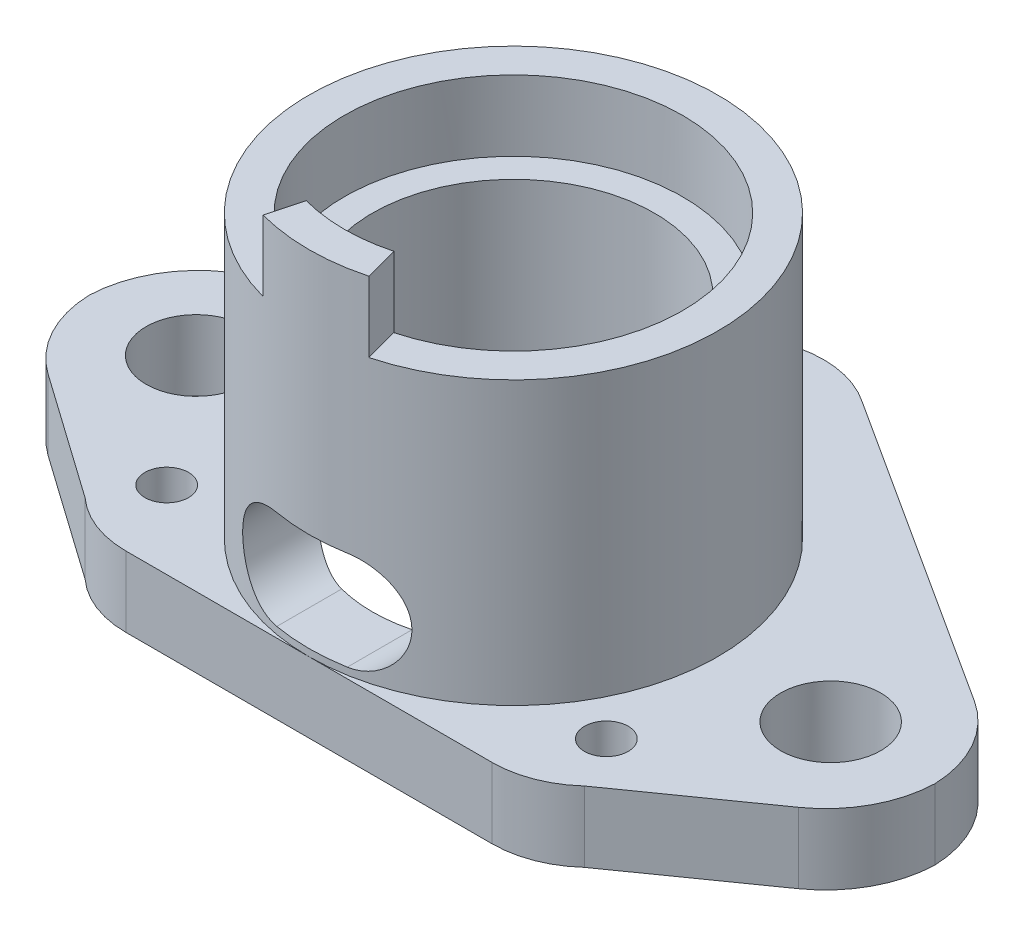
SolidWorks part; units mm, degrees
material "6061 Alloy"
ref_plane "Front Plane" through (0, 0, 0) normal (0, 0, 1) x (1, 0, 0)
ref_plane "Top Plane" through (0, 0, 0) normal (0, 1, 0) x (1, 0, 0)
ref_plane "Right Plane" through (0, 0, 0) normal (1, 0, 0) x (0, 0, -1)
sketch "Sketch1" plane through (0, 0, 0) normal (0, 1, 0) x (1, 0, 0)
  circle A0 centre (0, 0) radius 10
  circle A1 centre (0, 0) radius 14.5
  dimension "D1" = 29
  dimension "D2" = 20
extrude "Boss-Extrude1" add sketch "Sketch1" along normal mid plane 15
sketch "Sketch2" plane through (0, 7.5, 0) normal (0, 1, 0) x (1, 0, 0)
  circle A0 centre (0, 0) radius 14.5
  circle A1 centre (0, 0) radius 12
  dimension "D1" = 29
  dimension "D2" = 24
extrude "Boss-Extrude2" add sketch "Sketch2" along normal blind 5
sketch "Sketch3" plane through (0, -7.5, 0) normal (0, -1, 0) x (-1, 0, 0)
  line L0 (0, 0) -> (0, 38.6793) construction
  line L1 (0, 0) -> (-32.5079, 0) construction
  line L2 (0, 29) -> (-25.1147, -14.5)
  line L3 (-25.1147, -14.5) -> (25.1147, -14.5)
  line L4 (0, 29) -> (25.1147, -14.5)
  line L5 (0, 0) -> (25.1147, -14.5) construction
  circle A0 centre (0, 0) radius 12
  circle A1 centre (15.5885, -9) radius 1.55
  circle A2 centre (-15.5885, -9) radius 1.55
  circle A3 centre (0, 18) radius 1.55
  point P9 (0, -14.5)
  point P18 (0, 0)
  dimension "D1" = 24
  dimension "D4" = 18
  dimension "D5" = 3.1
  dimension "D2" = 120
  dimension "D3" = 14.5
  dimension "D6" = 3
extrude "Boss-Extrude3" add sketch "Sketch3" along normal blind 5
fillet "Fillet1" radius 7 3 edges at (-25.1147, -10, 14.5) (25.1147, -10, 14.5) (0, -10, -29)
sketch "Sketch4" plane through (0, 12.5, 0) normal (0, 1, 0) x (1, 0, 0)
  line L0 (0, 0) -> (0, -47.2539) construction
  line L1 (0, 0) -> (7.9041, -29.4985) construction
  line L2 (3.1058, -11.5911) -> (3.7529, -14.0059)
  line L3 (-3.1058, -11.5911) -> (-3.7529, -14.0059)
  circle A0 centre (0, 0) radius 12
  circle A1 centre (0, 0) radius 14.5
  circle M4 centre (0, 0) radius 14.5
  circle M5 centre (0, 0) radius 12
  dimension "D1" = 24
  dimension "D2" = 29
  dimension "D3" = 15
extrude "Boss-Extrude4" add sketch "Sketch4" along normal blind 5 contours L3 L2 M5 M4 region at (0, 12.5, 13.138)
sketch "Sketch5" plane through (0, 0, 0) normal (0, 0, 1) x (1, 0, 0)
  line L0 (0, 0) -> (0, -21.4052) construction
  line L1 (-2.5, -3.5) -> (2.5, -3.5) construction
  line L2 (-2.5, 0) -> (2.5, 0)
  line L3 (-2.5, -7) -> (2.5, -7)
  line L4 (12.9904, -12.5) -> (19.9904, -12.5) construction
  arc A0 (-2.5, 0) -> (-2.5, -7) centre (-2.5, -3.5) ccw
  arc A1 (2.5, -7) -> (2.5, 0) centre (2.5, -3.5) ccw
  point P5 (0, -3.5)
  dimension "D2" = 3.5
  dimension "D1" = 5
  dimension "D3" = 9
extrude "Cut-Extrude1" cut sketch "Sketch5" along normal through all
fillet "Fillet2" [suppressed] radius 2
sketch "草图1" plane through (0, -7.5, 0) normal (0, 1, 0) x (1, 0, 0)
  line L0 (-1000, 0) -> (49000, 0) construction
  line L1 (-30, -4) -> (-30, 4)
  line L2 (-30, 4) -> (-3.6287, 20.986)
  line L3 (-30, -4) -> (-17.7033, -12.6758)
  line L4 (0, 0) -> (0, -5.1927) construction
  line L5 (30, -4) -> (17.7033, -12.6758)
  line L6 (30, 4) -> (3.6287, 20.986)
  line L7 (30, -4) -> (30, 4)
  line L14 (12.5574, 7.25) -> (6.0622, 18.5)
  line L15 (-6.0622, 18.5) -> (-12.5574, 7.25)
  line L16 (12.5574, 7.25) -> (6.0622, 18.5)
  line L17 (-6.0622, 18.5) -> (-12.5574, 7.25)
  line L18 (0, -14.5) -> (12.9904, -14.5)
  line L19 (19.0526, -4) -> (12.5574, 7.25)
  line L20 (0, -14.5) -> (12.9904, -14.5)
  line L21 (19.0526, -4) -> (12.5574, 7.25)
  circle A0 centre (-22.5, 0) radius 3.55
  circle A1 centre (22.5, 0) radius 3.55
  arc A4 (6.0622, 18.5) -> (-6.0622, 18.5) centre (0, 15) ccw construction
  arc A5 (-19.0526, -4) -> (-12.9904, -14.5) centre (-12.9904, -7.5) ccw construction
  circle A8 centre (15.5885, -9) radius 1.55 construction
  circle A9 centre (15.5885, -9) radius 1.55
  arc A12 (6.0622, 18.5) -> (-6.0622, 18.5) centre (0, 15) ccw
  arc A13 (12.5574, 7.25) -> (-12.5574, 7.25) centre (0, 0) ccw
  arc A14 (6.0622, 18.5) -> (-6.0622, 18.5) centre (0, 15) ccw
  arc A15 (12.5574, 7.25) -> (-12.5574, 7.25) centre (0, 0) ccw
  arc A16 (12.9904, -14.5) -> (19.0526, -4) centre (12.9904, -7.5) ccw
  arc A17 (0, -14.5) -> (12.5574, 7.25) centre (0, 0) ccw
  arc A18 (12.9904, -14.5) -> (19.0526, -4) centre (12.9904, -7.5) ccw
  arc A19 (0, -14.5) -> (12.5574, 7.25) centre (0, 0) ccw
  point P10 (-30, 0)
  line M2 (-12.5574, 7.25) -> (-19.0526, -4)
  arc M3 (-19.0526, -4) -> (-12.9904, -14.5) centre (-12.9904, -7.5) ccw
  line M4 (-12.9904, -14.5) -> (0, -14.5)
  arc M5 (0, -14.5) -> (-12.5574, 7.25) centre (0, 0) cw
  circle M6 centre (-15.5885, -9) radius 1.55
  dimension "D1" = 7.1
  dimension "D2" = 7.1
  dimension "D3" = 22.5
  dimension "D4" = 22.5
  dimension "D5" = 30
  dimension "D6" = 4
  dimension "D8" = 0
  dimension "D9" = 0
extrude "凸台-拉伸1" add sketch "草图1" against normal up to surface (5 mm away) contours A14 L2 L1 L3 L17 A0 M3 M2 | A18 L5 L7 L6 A14 L16 L21 A1 | M5 M2 M3 M4 M6 | A19 L20 A18 L21 region at (-19.7203, -7.5, -4.0937) region at (-19.6153, -7.5, 8.5303) region at (12.8132, -7.5, 7.3977) region at (19.7203, -7.5, -4.0937) up to face at (15.5885, -12.5, 7.45)
fillet "圆角1" radius 8 4 edges at (30, -10, -4) (30, -10, 4) (-30, -10, -4) (-30, -10, 4)
